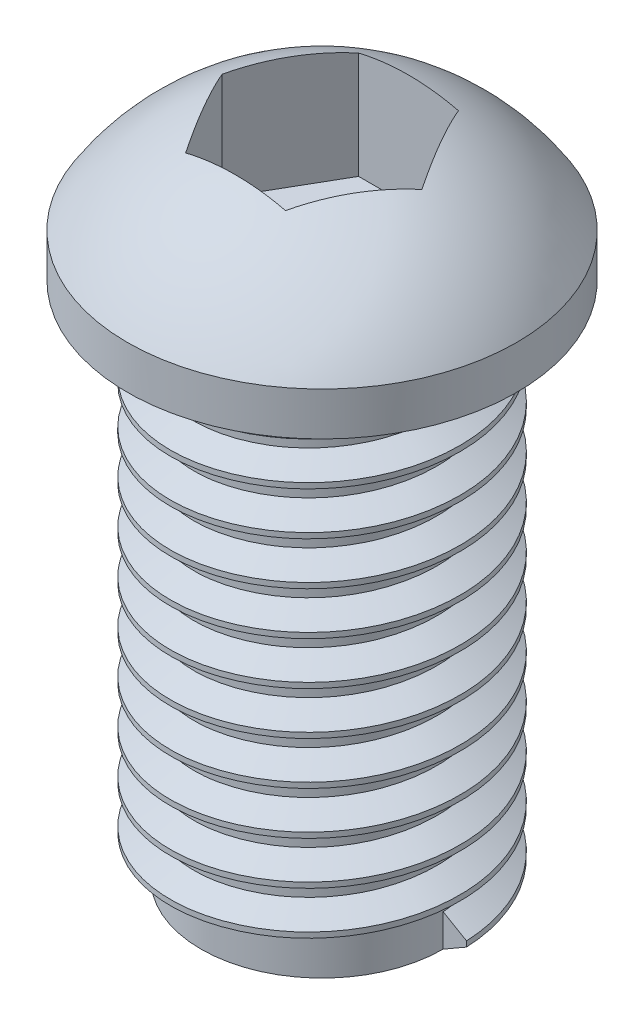
SolidWorks part; units mm, degrees
ref_plane "Front Plane" through (0, 0, 0) normal (0, 0, 1) x (1, 0, 0)
ref_plane "Top Plane" through (0, 0, 0) normal (0, 1, 0) x (1, 0, 0)
ref_plane "Right Plane" through (0, 0, 0) normal (1, 0, 0) x (0, 0, -1)
sketch "Sketch1" plane through (0, 0, 0) normal (0, 1, 0) x (1, 0, 0)
  circle A0 centre (0, 0) radius 1.4
  dimension "D1" = 2.8
extrude "Boss-Extrude1" add sketch "Sketch1" against normal blind 6
sketch "Sketch2" plane through (0, 0, 0) normal (0, 0, 1) x (1, 0, 0)
  line L0 (0, 0) -> (2.25, 0)
  line L1 (2.25, 0) -> (2.25, 0.5)
  line L2 (0, 0) -> (0, 1.75)
  arc A0 (0, 1.75) -> (2.25, 0.5) centre (0, -0.9) cw
  dimension "D1" = 2.25
  dimension "D2" = 0.5
  dimension "D3" = 1.75
revolve "Revolve1" add sketch "Sketch2" angle 360 about L2
sketch "Sketch3" plane through (0, 0, 0) normal (0, 1, 0) x (1, 0, 0)
  line L1 (1.1547, 0) -> (0.5774, 1)
  line L2 (0.5774, 1) -> (-0.5774, 1)
  line L3 (-0.5774, 1) -> (-1.1547, 0)
  line L4 (-1.1547, 0) -> (-0.5774, -1)
  line L5 (-0.5774, -1) -> (0.5774, -1)
  line L6 (0.5774, -1) -> (1.1547, 0)
  circle A0 centre (0, 0) radius 1 construction
  dimension "D1" = 2
  dimension "D2" = 1
extrude "Cut-Extrude1" cut sketch "Sketch3" against normal blind 1.5 from offset 1.75
thread "Thread2" pitch 0.5 method extrude profile "Thread Profile2" start angle 0, offset 0, length 0, pitch 0.5, diameter 2.8
ref_plane "Plane2" through (1.4, -6, 0) normal (0, 0, 1) x (1, 0, 0)
sketch "Thread Profile2" plane through (1.4, -6, 0) normal (0, 0, 1) x (1, 0, 0)
  line L0 (0, 0) -> (0, 0.5) construction
  line L1 (0, 0) -> (0.2706, 0.1562)
  line L2 (0.2706, 0.1562) -> (0.2706, 0.2187)
  line L3 (0.2706, 0.2187) -> (0, 0.375)
  line L4 (0.2706, 0.1875) -> (0, 0.1875) construction
  line L11 (0, 0) -> (0, 0.375)
  point P2 (0, 0)
  dimension "Pitch" = 0.5
  dimension "Profile_Angle" = 60
  dimension "Profile_Land" = 0.0625
  dimension "Profile_Height" = 0.2706
